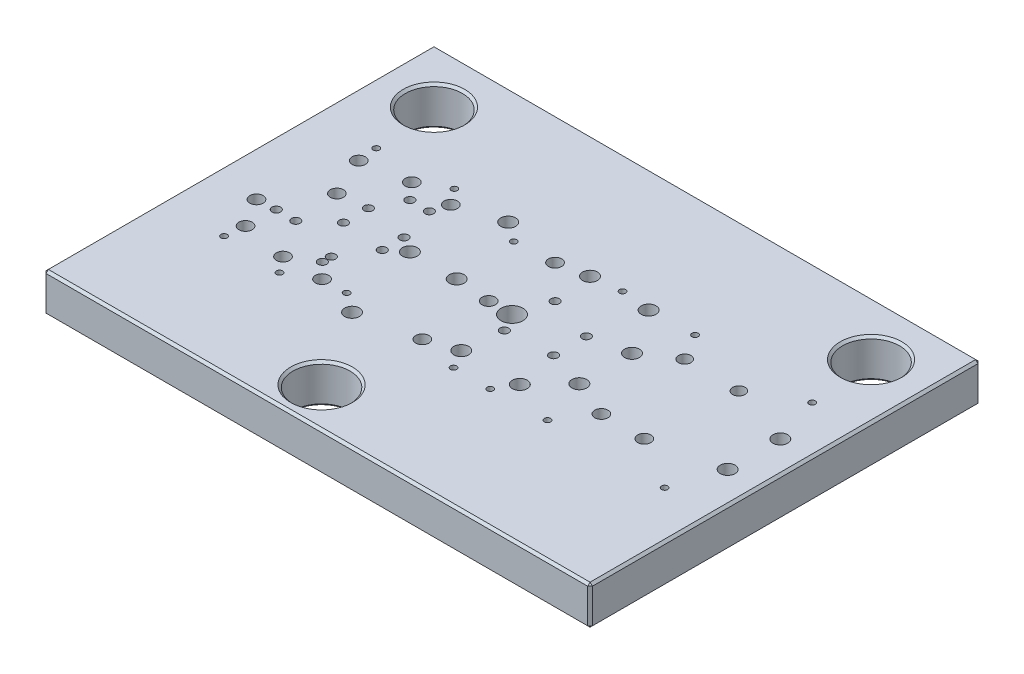
SolidWorks part; units mm, degrees
material "Plain Carbon Steel"
ref_plane "Front Plane" through (0, 0, 0) normal (0, 0, 1) x (1, 0, 0)
ref_plane "Top Plane" through (0, 0, 0) normal (0, 1, 0) x (1, 0, 0)
ref_plane "Right Plane" through (0, 0, 0) normal (1, 0, 0) x (0, 0, -1)
sketch "Sketch1" plane through (0, 0, 0) normal (0, 1, 0) x (1, 0, 0)
  line L1 (-350, -250) -> (350, -250)
  line L2 (-350, -250) -> (-350, 250)
  line L3 (-350, 250) -> (350, 250)
  line L4 (350, -250) -> (350, 250)
  line L5 (-350, -250) -> (350, 250) construction
  line L6 (-350, 250) -> (350, -250) construction
  point P0 (0, 0)
  dimension "D1" = 700
  dimension "D2" = 500
extrude "Boss-Extrude1" add sketch "Sketch1" against normal blind 50
sketch "Sketch2" plane through (0, 0, 0) normal (0, 1, 0) x (1, 0, 0)
  line L0 (350, 250) -> (-350, 250) construction
  line L1 (-350, 250) -> (-350, -250) construction
  line L2 (350, -250) -> (350, 250) construction
  line L3 (-350, -250) -> (350, -250) construction
  circle A0 centre (-280, 180) radius 36.5
  circle A1 centre (280, 180) radius 36.5
  circle A2 centre (-44, -200) radius 36.5
  dimension "D1" = 73
  dimension "D2" = 70
  dimension "D3" = 70
  dimension "D4" = 70
  dimension "D5" = 50
  dimension "D6" = 44
extrude "Cut-Extrude1" cut sketch "Sketch2" against normal up to next
chamfer "Chamfer1" distance 3 angle 45 6 edges at (280, -50, -216.5) (280, 0, -143.5) (-280, -50, -216.5) (-280, 0, -143.5) (-44, -50, 163.5) (-44, 0, 236.5)
chamfer "Chamfer2" distance 3 angle 45 12 edges at (-350, -25, -250) (-350, -25, 250) (350, -25, -250) (0, -50, -250) (-350, -50, 0) (0, -50, 250) (350, -50, 0) (350, -25, 250) (350, 0, 0) (0, 0, -250) (-350, 0, 0) (0, 0, 250)
hole_wizard "M30x2.0 Tapped Hole1" positions "Sketch5" profile "Sketch4" tap size "M30x2.0" standard "ISO" end condition through all
sketch "Sketch5" plane through (0, 0, 0) normal (0, 1, 0) x (1, 0, 0)
  point P0 (0, 0)
sketch "Sketch4" plane through (0, 0, 0) normal (1, 0, 0) x (0, 0, 1)
  line L0 (0, 0) -> (0, 50)
  line L1 (0, 50) -> (14, 50)
  line L2 (14, 50) -> (14, 0)
  line L5 (14, 0) -> (0, 0)
  line L11 (0, -6.35) -> (0, 107.95) construction
  dimension "Thru Tap Drill Dia." = 28
  dimension "Thru Tap Drill Depth" = 50
cosmetic thread "Hole Thread1"
sketch "Sketch7" plane through (0, 0, 0) normal (0, 1, 0) x (1, 0, 0)
  circle A0 centre (310, 33.75) radius 6
  circle A1 centre (310, -33.75) radius 6
  circle A2 centre (120, -33.75) radius 6
  circle A3 centre (120, 33.75) radius 6
  dimension "D1" = 12
extrude "Cut-Extrude2" cut sketch "Sketch7" against normal up to next
sketch "Sketch8" plane through (0, 0, 0) normal (0, 1, 0) x (1, 0, 0)
  circle A0 centre (222.63, -53.14) radius 8.5
  circle A1 centre (167.63, -53.14) radius 8.5
  dimension "D1" = 17
extrude "Cut-Extrude3" cut sketch "Sketch8" against normal up to next
sketch "Sketch9" plane through (0, 0, 0) normal (0, 1, 0) x (1, 0, 0)
  circle A0 centre (160.13, 61.13) radius 8
  circle A1 centre (230.13, 60.5) radius 8
  dimension "D1" = 16
extrude "Cut-Extrude4" cut sketch "Sketch9" against normal up to next
sketch "Sketch11" plane through (0, 0, 0) normal (0, 1, 0) x (1, 0, 0)
  circle A0 centre (310, -33.75) radius 9.5
  circle A1 centre (310, 33.75) radius 9.5
  circle A2 centre (120, -33.75) radius 9.5
  circle A3 centre (120, 33.75) radius 9.5
  dimension "D1" = 19
extrude "Cut-Extrude5" cut sketch "Sketch11" against normal blind 36.8
hole_wizard "M10 Tapped Hole1" positions "Sketch14" profile "Sketch13" tap size "M10" standard "ISO"
sketch "Sketch14" plane through (0, -50, 0) normal (0, -1, 0) x (-1, 0, 0)
  point P0 (-307, -94.5)
  point P3 (-123, -94.5)
  point P6 (-123, 94.5)
  point P9 (-307, 94.5)
sketch "Sketch13" plane through (307, -50, 94.5) normal (1, 0, 0) x (0, 0, -1)
  line L0 (0, 0) -> (0, 30.0537)
  line L1 (0, 30.0537) -> (4.25, 27.5)
  line L2 (4.25, 27.5) -> (4.25, 0)
  line L5 (4.25, 0) -> (0, 0)
  line L10 (0, 30.0537) -> (-4.25, 27.5) construction
  line L11 (0, -6.35) -> (0, 107.95) construction
  dimension "Tap Drill Dia." = 8.5
  dimension "Tap Drill Depth" = 27.5
  dimension "Drill Angle" = 118
cosmetic thread "Hole Thread2"
cosmetic thread "Hole Thread3"
cosmetic thread "Hole Thread4"
cosmetic thread "Hole Thread5"
hole_wizard "Ø8.0mm Dowel Hole1" positions "Sketch17" profile "Sketch16" hole size "Ø8.0" standard "ISO" end condition through all
sketch "Sketch17" plane through (0, 0, 0) normal (0, 1, 0) x (1, 0, 0)
  point P0 (290, 94.5)
  point P3 (140, 94.5)
  point P6 (290, -94.5)
  point P9 (140, -94.5)
sketch "Sketch16" plane through (290, 0, -94.5) normal (1, 0, 0) x (0, 0, 1)
  line L0 (0, 0) -> (0, 50)
  line L1 (0, 50) -> (4, 50)
  line L2 (4, 50) -> (4, 0)
  line L5 (4, 0) -> (0, 0)
  line L11 (0, -6.35) -> (0, 107.95) construction
  dimension "Thru Hole Dia." = 8
  dimension "Thru Hole Depth" = 50
hole_wizard "M8 Tapped Hole1" positions "Sketch20" profile "Sketch19" tap size "M8" standard "ISO"
sketch "Sketch20" plane through (0, -50, 0) normal (0, 1, 0) x (1, 0, 0)
  point P0 (62.13, 96.5)
  point P3 (28.13, 96.5)
  point P6 (84.13, -96.5)
  point P9 (6.13, -96.5)
sketch "Sketch19" plane through (62.13, -50, -96.5) normal (1, 0, 0) x (0, 0, -1)
  line L0 (0, 0) -> (0, 24.2929)
  line L1 (0, 24.2929) -> (3.4, 22.25)
  line L2 (3.4, 22.25) -> (3.4, 0)
  line L5 (3.4, 0) -> (0, 0)
  line L10 (0, 24.2929) -> (-3.4, 22.25) construction
  line L11 (0, -6.35) -> (0, 107.95) construction
  dimension "Tap Drill Dia." = 6.8
  dimension "Tap Drill Depth" = 22.25
  dimension "Drill Angle" = 118
cosmetic thread "Hole Thread6"
cosmetic thread "Hole Thread7"
cosmetic thread "Hole Thread8"
cosmetic thread "Hole Thread9"
hole_wizard "Ø8.0mm Dowel Hole2" positions "Sketch23" profile "Sketch22" hole size "Ø8.0" standard "ISO" end condition through all
sketch "Sketch23" plane through (0, 0, 0) normal (0, 1, 0) x (1, 0, 0)
  point P0 (68.63, -96.5)
  point P3 (21.63, -96.5)
  point P6 (45.13, 96.5)
sketch "Sketch22" plane through (68.63, 0, 96.5) normal (1, 0, 0) x (0, 0, 1)
  line L0 (0, 0) -> (0, 50)
  line L1 (0, 50) -> (4, 50)
  line L2 (4, 50) -> (4, 0)
  line L5 (4, 0) -> (0, 0)
  line L11 (0, -6.35) -> (0, 107.95) construction
  dimension "Thru Hole Dia." = 8
  dimension "Thru Hole Depth" = 50
hole_wizard "Ø11.0 (11) Diameter Hole1" positions "Sketch26" profile "Sketch25" hole size "Ø11.0" standard "ISO" end condition through all
sketch "Sketch26" plane through (0, 0, 0) normal (0, 1, 0) x (1, 0, 0)
  point P0 (71.88, -18.64)
  point P3 (12.88, -22.64)
  point P6 (71.88, 23.36)
  point P9 (12.88, 42.36)
sketch "Sketch25" plane through (71.88, 0, 18.64) normal (1, 0, 0) x (0, 0, 1)
  line L0 (0, 0) -> (0, 50)
  line L1 (0, 50) -> (5.5, 50)
  line L2 (5.5, 50) -> (5.5, 0)
  line L5 (5.5, 0) -> (0, 0)
  line L11 (0, -6.35) -> (0, 107.95) construction
  dimension "Thru Hole Dia." = 11
  dimension "Thru Hole Depth" = 50
sketch "Sketch27" plane through (0, 0, 0) normal (0, 1, 0) x (1, 0, 0)
  circle A0 centre (7.63, 92.36) radius 6
  circle A1 centre (82.63, 92.36) radius 6
  circle A2 centre (82.63, -72.64) radius 6
  circle A3 centre (7.63, -72.64) radius 6
  dimension "D1" = 12
extrude "Cut-Extrude6" cut sketch "Sketch27" against normal through all
sketch "Sketch29" plane through (0, 0, 0) normal (0, 1, 0) x (1, 0, 0)
  circle A0 centre (7.63, 92.36) radius 9.5
  circle A1 centre (82.63, 92.36) radius 9.5
  circle A2 centre (7.63, -72.64) radius 9.5
  circle A3 centre (82.63, -72.64) radius 9.5
  dimension "D1" = 19
extrude "Cut-Extrude7" cut sketch "Sketch29" against normal blind 36.8
sketch "Sketch30" plane through (0, 0, 0) normal (0, 1, 0) x (1, 0, 0)
  circle A0 centre (-29.87, 85) radius 5
  circle A1 centre (-29.87, 0) radius 5
  circle A2 centre (-29.87, -85) radius 5
  dimension "D1" = 10
extrude "Cut-Extrude8" cut sketch "Sketch30" against normal through all
sketch "Sketch31" plane through (0, 0, 0) normal (0, 1, 0) x (1, 0, 0)
  circle A0 centre (-29.87, 85) radius 8.5
  circle A1 centre (-29.87, 0) radius 8.5
  circle A2 centre (-29.87, -85) radius 8.5
  dimension "D1" = 17
extrude "Cut-Extrude9" cut sketch "Sketch31" against normal blind 39.8
hole_wizard "M8 Tapped Hole2" positions "Sketch34" profile "Sketch33" tap size "M8" standard "ISO"
sketch "Sketch34" plane through (0, -50, 0) normal (0, -1, 0) x (-1, 0, 0)
  point P0 (79.87, -97.5)
  point P3 (129.87, -97.5)
  point P6 (79.87, 97.5)
  point P9 (129.87, 97.5)
sketch "Sketch33" plane through (-79.87, -50, 97.5) normal (1, 0, 0) x (0, 0, -1)
  line L0 (0, 0) -> (0, 24.2929)
  line L1 (0, 24.2929) -> (3.4, 22.25)
  line L2 (3.4, 22.25) -> (3.4, 0)
  line L5 (3.4, 0) -> (0, 0)
  line L10 (0, 24.2929) -> (-3.4, 22.25) construction
  line L11 (0, -6.35) -> (0, 107.95) construction
  dimension "Tap Drill Dia." = 6.8
  dimension "Tap Drill Depth" = 22.25
  dimension "Drill Angle" = 118
cosmetic thread "Hole Thread10"
cosmetic thread "Hole Thread11"
cosmetic thread "Hole Thread12"
cosmetic thread "Hole Thread13"
hole_wizard "Ø8.0mm Dowel Hole3" positions "Sketch37" profile "Sketch36" hole size "Ø8.0" standard "ISO" end condition through all
sketch "Sketch37" plane through (0, 0, 0) normal (0, 1, 0) x (1, 0, 0)
  point P0 (-79.87, 81.975)
  point P3 (-129.87, -82)
sketch "Sketch36" plane through (-79.87, 0, -81.975) normal (1, 0, 0) x (0, 0, 1)
  line L0 (0, 0) -> (0, 50)
  line L1 (0, 50) -> (4, 50)
  line L2 (4, 50) -> (4, 0)
  line L5 (4, 0) -> (0, 0)
  line L11 (0, -6.35) -> (0, 107.95) construction
  dimension "Thru Hole Dia." = 8
  dimension "Thru Hole Depth" = 50
sketch "Sketch38" plane through (0, 0, 0) normal (0, 1, 0) x (1, 0, 0)
  circle A0 centre (-104.87, 100) radius 6 construction
  circle A1 centre (-104.87, -100) radius 6 construction
  circle A2 centre (-104.87, 100) radius 6
  circle A3 centre (-104.87, -100) radius 6
  circle A4 centre (-74.87, 4) radius 6 construction
  circle A5 centre (-74.87, 4) radius 6
  circle A6 centre (-134.87, 4) radius 6 construction
  circle A7 centre (-134.87, 4) radius 6
extrude "Cut-Extrude10" cut sketch "Sketch38" against normal through all
sketch "Sketch39" plane through (0, 0, 0) normal (0, 1, 0) x (1, 0, 0)
  circle A0 centre (-104.87, 100) radius 9.5
  circle A1 centre (-104.87, -100) radius 9.5
  circle A2 centre (-74.87, 4) radius 9.5
  circle A3 centre (-134.87, 4) radius 9.5
  dimension "D1" = 19
extrude "Cut-Extrude11" cut sketch "Sketch39" against normal blind 36.8
sketch "Sketch40" plane through (0, -50, 0) normal (0, -1, 0) x (1, 0, 0)
  circle A0 centre (-185.87, -82.5) radius 10 construction
  circle A1 centre (-210.87, 82.5) radius 10 construction
  circle A2 centre (-185.87, 82.5) radius 10 construction
  circle A3 centre (-160.87, 82.5) radius 10 construction
  circle A4 centre (-160.87, 33) radius 10 construction
  circle A5 centre (-210.87, 33) radius 10 construction
  circle A6 centre (-160.87, -39) radius 10 construction
  circle A7 centre (-160.87, -82.5) radius 10 construction
  circle A8 centre (-210.87, -82.5) radius 10 construction
  circle A9 centre (-210.87, -47) radius 10 construction
  circle A10 centre (-185.87, -82.5) radius 10
  circle A11 centre (-210.87, 82.5) radius 10
  circle A12 centre (-185.87, 82.5) radius 10
  circle A13 centre (-160.87, 82.5) radius 10
  circle A14 centre (-160.87, 33) radius 10
  circle A15 centre (-210.87, 33) radius 10
  circle A16 centre (-160.87, -39) radius 10
  circle A17 centre (-160.87, -82.5) radius 10
  circle A18 centre (-210.87, -82.5) radius 10
  circle A19 centre (-210.87, -47) radius 10
extrude "Cut-Extrude12" cut sketch "Sketch40" against normal blind 9.2
hole_wizard "Ø10.0 (10) Diameter Hole1" positions "Sketch44" profile "Sketch43" hole size "Ø10.0" standard "ISO" end condition through all
sketch "Sketch44" plane through (0, 0, 0) normal (0, 1, 0) x (1, 0, 0)
  point P0 (-160.87, 82.5)
  point P3 (-210.87, 82.5)
  point P6 (-160.87, -82.5)
  point P9 (-210.87, -82.5)
sketch "Sketch43" plane through (-160.87, 0, -82.5) normal (1, 0, 0) x (0, 0, 1)
  line L0 (0, 0) -> (0, 50)
  line L1 (0, 50) -> (5, 50)
  line L2 (5, 50) -> (5, 0)
  line L5 (5, 0) -> (0, 0)
  line L11 (0, -6.35) -> (0, 107.95) construction
  dimension "Thru Hole Dia." = 10
  dimension "Thru Hole Depth" = 50
sketch "Sketch45" plane through (0, 0, 0) normal (0, 1, 0) x (1, 0, 0)
  circle A0 centre (-160.87, 82.5) radius 8.5
  circle A1 centre (-210.87, 82.5) radius 8.5
  circle A2 centre (-160.87, -82.5) radius 8.5
  circle A3 centre (-210.87, -82.5) radius 8.5
  dimension "D1" = 17
extrude "Cut-Extrude13" cut sketch "Sketch45" against normal blind 33.8
hole_wizard "Ø11.0 (11) Diameter Hole2" positions "Sketch48" profile "Sketch47" hole size "Ø11.0" standard "ISO" end condition through all
sketch "Sketch48" plane through (0, 0, 0) normal (0, 1, 0) x (1, 0, 0)
  point P0 (-167.37, 61.5)
  point P3 (-192.37, 61.5)
  point P6 (-154.62, 16.36)
  point P9 (-209.87, 25.86)
  point P12 (-209.87, -6.14)
  point P15 (-179.87, -51.64)
  point P20 (-179.87, -63.14)
  point P23 (-154.62, -11.64)
sketch "Sketch47" plane through (-167.37, 0, -61.5) normal (1, 0, 0) x (0, 0, 1)
  line L0 (0, 0) -> (0, 50)
  line L1 (0, 50) -> (5.5, 50)
  line L2 (5.5, 50) -> (5.5, 0)
  line L5 (5.5, 0) -> (0, 0)
  line L11 (0, -6.35) -> (0, 107.95) construction
  dimension "Thru Hole Dia." = 11
  dimension "Thru Hole Depth" = 50
hole_wizard "M8 Tapped Hole3" positions "Sketch53" profile "Sketch52" tap size "M8" standard "ISO"
sketch "Sketch53" plane through (0, -50, 0) normal (0, -1, 0) x (-1, 0, 0)
  point P0 (160.87, -102.5)
  point P3 (210.87, -102.5)
  point P6 (160.87, 102.5)
  point P9 (210.87, 102.5)
sketch "Sketch52" plane through (-160.87, -50, 102.5) normal (1, 0, 0) x (0, 0, -1)
  line L0 (0, 0) -> (0, 24.2929)
  line L1 (0, 24.2929) -> (3.4, 22.25)
  line L2 (3.4, 22.25) -> (3.4, 0)
  line L5 (3.4, 0) -> (0, 0)
  line L10 (0, 24.2929) -> (-3.4, 22.25) construction
  line L11 (0, -6.35) -> (0, 107.95) construction
  dimension "Tap Drill Dia." = 6.8
  dimension "Tap Drill Depth" = 22.25
  dimension "Drill Angle" = 118
cosmetic thread "Hole Thread14"
cosmetic thread "Hole Thread15"
cosmetic thread "Hole Thread16"
cosmetic thread "Hole Thread17"
hole_wizard "Ø8.0mm Dowel Hole4" positions "Sketch56" profile "Sketch55" hole size "Ø8.0" standard "ISO" end condition through all
sketch "Sketch56" plane through (0, 0, 0) normal (0, 1, 0) x (1, 0, 0)
  point P0 (-176.37, 102.5)
  point P3 (-195.37, -102.5)
sketch "Sketch55" plane through (-176.37, 0, -102.5) normal (1, 0, 0) x (0, 0, 1)
  line L0 (0, 0) -> (0, 50)
  line L1 (0, 50) -> (4, 50)
  line L2 (4, 50) -> (4, 0)
  line L5 (4, 0) -> (0, 0)
  line L11 (0, -6.35) -> (0, 107.95) construction
  dimension "Thru Hole Dia." = 8
  dimension "Thru Hole Depth" = 50
sketch "Sketch57" plane through (0, 0, 0) normal (0, 1, 0) x (1, 0, 0)
  circle A0 centre (-268.87, -72.5) radius 5 construction
  circle A1 centre (-291.37, -36) radius 5 construction
  circle A2 centre (-246.37, 22) radius 5 construction
  circle A3 centre (-268.87, 72.5) radius 5 construction
  circle A4 centre (-268.87, -72.5) radius 5
  circle A5 centre (-291.37, -36) radius 5
  circle A6 centre (-246.37, 22) radius 5
  circle A7 centre (-268.87, 72.5) radius 5
extrude "Cut-Extrude14" cut sketch "Sketch57" against normal through all
sketch "Sketch58" plane through (0, 0, 0) normal (0, 1, 0) x (1, 0, 0)
  circle A0 centre (-268.87, 72.5) radius 8.5
  circle A1 centre (-246.37, 22) radius 8.5
  circle A2 centre (-291.37, -36) radius 8.5
  circle A3 centre (-268.87, -72.5) radius 8.5
  dimension "D1" = 17
extrude "Cut-Extrude15" cut sketch "Sketch58" against normal blind 36.8
hole_wizard "Ø11.0 (11) Diameter Hole3" positions "Sketch61" profile "Sketch60" hole size "Ø11.0" standard "ISO" end condition through all
sketch "Sketch61" plane through (0, 0, 0) normal (0, 1, 0) x (1, 0, 0)
  point P0 (-267.37, -34.64)
  point P3 (-242.37, -34.64)
sketch "Sketch60" plane through (-267.37, 0, 34.64) normal (1, 0, 0) x (0, 0, 1)
  line L0 (0, 0) -> (0, 50)
  line L1 (0, 50) -> (5.5, 50)
  line L2 (5.5, 50) -> (5.5, 0)
  line L5 (5.5, 0) -> (0, 0)
  line L11 (0, -6.35) -> (0, 107.95) construction
  dimension "Thru Hole Dia." = 11
  dimension "Thru Hole Depth" = 50
hole_wizard "M8 Tapped Hole4" positions "Sketch64" profile "Sketch63" tap size "M8" standard "ISO"
sketch "Sketch64" plane through (0, -50, 0) normal (0, 1, 0) x (1, 0, 0)
  point P0 (-291.37, 97.5)
  point P3 (-251.37, 97.5)
  point P6 (-251.37, -97.5)
  point P9 (-291.37, -97.5)
sketch "Sketch63" plane through (-291.37, -50, -97.5) normal (1, 0, 0) x (0, 0, -1)
  line L0 (0, 0) -> (0, 24.2929)
  line L1 (0, 24.2929) -> (3.4, 22.25)
  line L2 (3.4, 22.25) -> (3.4, 0)
  line L5 (3.4, 0) -> (0, 0)
  line L10 (0, 24.2929) -> (-3.4, 22.25) construction
  line L11 (0, -6.35) -> (0, 107.95) construction
  dimension "Tap Drill Dia." = 6.8
  dimension "Tap Drill Depth" = 22.25
  dimension "Drill Angle" = 118
cosmetic thread "Hole Thread18"
cosmetic thread "Hole Thread19"
cosmetic thread "Hole Thread20"
cosmetic thread "Hole Thread21"
hole_wizard "Ø8.0mm Dowel Hole5" positions "Sketch67" profile "Sketch66" hole size "Ø8.0" standard "ISO" end condition through all
sketch "Sketch67" plane through (0, 0, 0) normal (0, 1, 0) x (1, 0, 0)
  point P0 (-271.37, -97.5)
  point P3 (-271.37, 97.5)
sketch "Sketch66" plane through (-271.37, 0, 97.5) normal (1, 0, 0) x (0, 0, 1)
  line L0 (0, 0) -> (0, 50)
  line L1 (0, 50) -> (4, 50)
  line L2 (4, 50) -> (4, 0)
  line L5 (4, 0) -> (0, 0)
  line L11 (0, -6.35) -> (0, 107.95) construction
  dimension "Thru Hole Dia." = 8
  dimension "Thru Hole Depth" = 50
